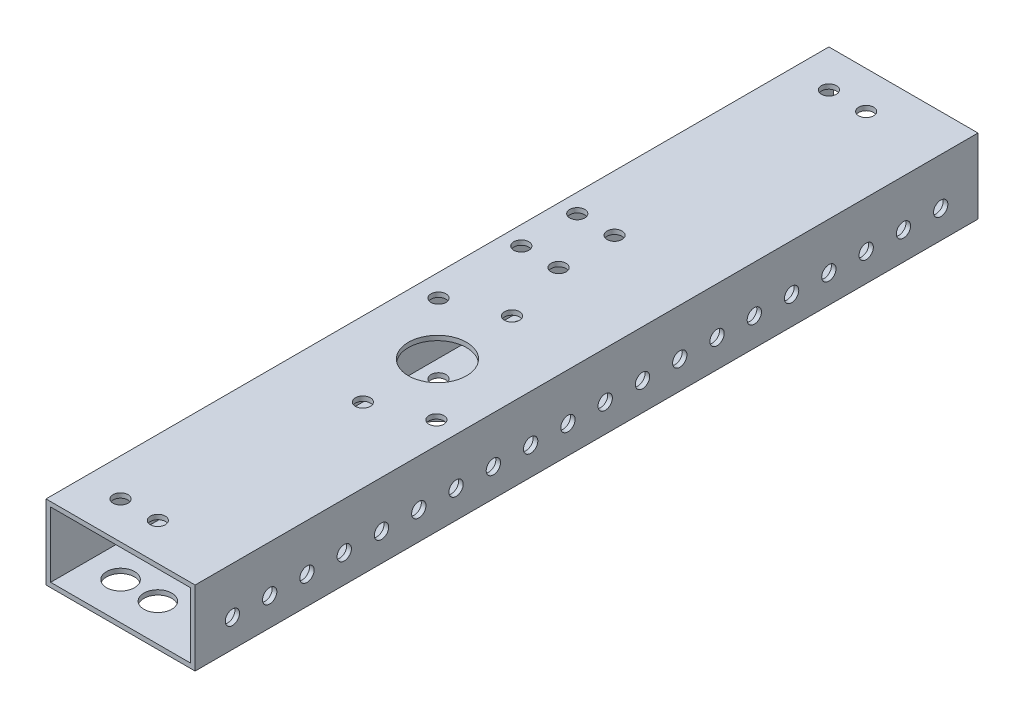
SolidWorks part; units mm, degrees
other "Markup1"
sketch "Sketch7" plane through (25.4, 12.7, -127) normal (0.9965, 0.0171, -0.0817) x (-0.082, 0.0128, -0.9966)
sketch "Sketch8" plane through (25.4, 12.7, -127) normal (0.9965, 0.0171, -0.0817) x (-0.082, 0.0128, -0.9966)
sketch "Sketch9" plane through (25.4, 12.7, -127) normal (0.9965, 0.0171, -0.0817) x (-0.082, 0.0128, -0.9966)
sketch "Sketch12" plane through (25.4, 12.7, -127) normal (0.9965, 0.0171, -0.0817) x (-0.082, 0.0128, -0.9966)
sketch "Sketch13" plane through (25.4, 12.7, -127) normal (0.9965, 0.0171, -0.0817) x (-0.082, 0.0128, -0.9966)
sketch "Sketch14" plane through (25.4, 12.7, -127) normal (0.9965, 0.0171, -0.0817) x (-0.082, 0.0128, -0.9966)
sketch "Sketch15" plane through (25.4, 12.7, -133.35) normal (0.9965, 0.0171, -0.0817) x (-0.082, 0.0128, -0.9966)
sketch "Sketch16" plane through (25.4, 12.7, -133.35) normal (0.9965, 0.0171, -0.0817) x (-0.082, 0.0128, -0.9966)
sketch "Sketch17" plane through (25.4, 12.7, -133.35) normal (0.9965, 0.0171, -0.0817) x (-0.082, 0.0128, -0.9966)
sketch "Sketch18" plane through (25.4, 12.7, -133.35) normal (0.9965, 0.0171, -0.0817) x (-0.082, 0.0128, -0.9966)
sketch "Sketch19" plane through (25.4, 12.7, -133.35) normal (0.9965, 0.0171, -0.0817) x (-0.082, 0.0128, -0.9966)
material "6061-T6 (SS)"
ref_plane "Front Plane" through (0, 0, 0) normal (0, 0, 1) x (1, 0, 0)
ref_plane "Top Plane" through (0, 0, 0) normal (0, 1, 0) x (1, 0, 0)
ref_plane "Right Plane" through (0, 0, 0) normal (1, 0, 0) x (0, 0, -1)
sketch "Sketch1" plane through (0, 0, 0) normal (0, 0, 1) x (1, 0, 0)
  line L0 (-23.8125, 11.1125) -> (23.8125, 11.1125)
  line L1 (-25.4, -12.7) -> (25.4, -12.7)
  line L2 (-25.4, -12.7) -> (-25.4, 12.7)
  line L3 (-25.4, 12.7) -> (25.4, 12.7)
  line L4 (25.4, -12.7) -> (25.4, 12.7)
  line L5 (-25.4, -12.7) -> (25.4, 12.7) construction
  line L6 (-25.4, 12.7) -> (25.4, -12.7) construction
  line L7 (23.8125, -11.1125) -> (23.8125, 11.1125)
  line L8 (-23.8125, -11.1125) -> (23.8125, -11.1125)
  line L9 (-23.8125, -11.1125) -> (-23.8125, 11.1125)
  point P0 (0, 0)
  dimension "D1" = 50.8
  dimension "D2" = 25.4
  dimension "D3" = 1.5875
extrude "Boss-Extrude1" add sketch "Sketch1" along normal mid plane 266.7
sketch "Sketch3" plane through (0, 12.7, 0) normal (0, 1, 0) x (1, 0, 0)
  line L0 (25.4, 133.35) -> (-25.4, 133.35) construction
  line L1 (25.4, -133.35) -> (-25.4, -133.35) construction
  line L3 (-25.4, -133.35) -> (-25.4, 133.35) construction
  line L4 (25.4, -133.35) -> (25.4, 133.35) construction
  circle A0 centre (-12.7, -120.65) radius 2.5527
  circle A1 centre (0, -120.65) radius 2.5527
  circle A2 centre (-12.7, 120.65) radius 2.5527
  circle A3 centre (0, 120.65) radius 2.5527
  dimension "D5" = 5.1054
  dimension "D1" = 12.7
  dimension "D2" = 12.7
  dimension "D3" = 12.7
  dimension "D4" = 12.7
  dimension "D6" = 12.7
  dimension "D7" = 12.7
  dimension "D8" = 12.7
  dimension "D9" = 25.4
  dimension "D10" = 12.7
  dimension "D11" = 25.4
extrude "Cut-Extrude1" cut sketch "Sketch3" against normal up to surface (1.5875 mm away) up to face at (0, 11.1125, 0)
sketch "Sketch5" plane through (0, -12.7, 0) normal (0, -1, 0) x (1, 0, 0)
  circle A0 centre (-12.7, -120.65) radius 2.5527 construction
  circle A1 centre (0, -120.65) radius 2.5527 construction
  circle A2 centre (0, 120.65) radius 2.5527 construction
  circle A3 centre (-12.7, 120.65) radius 2.5527 construction
  circle A4 centre (-12.7, -120.65) radius 2.5527
  circle A5 centre (0, -120.65) radius 2.5527
  circle A6 centre (0, 120.65) radius 2.5527
  circle A7 centre (-12.7, 120.65) radius 2.5527
  circle A8 centre (-12.7, 120.65) radius 4.7625
  circle A9 centre (0, 120.65) radius 4.7625
  circle A10 centre (0, -120.65) radius 4.7625
  circle A11 centre (-12.7, -120.65) radius 4.7625
  dimension "D1" = 9.525
extrude "Cut-Extrude2" cut sketch "Sketch5" against normal up to surface (1.5875 mm away) contours A10 A5 | A5 | A11 A4 | A4 | A6 | A9 A6 | A8 A7 | A7 region at (-12.7, -12.7, -120.65) region at (0, -12.7, -120.65) region at (0, -12.7, 120.65) region at (-12.7, -12.7, 120.65) region at (-17.3278, -12.7, 120.65) region at (-4.6278, -12.7, 120.65) region at (-4.6278, -12.7, -120.65) region at (-17.3278, -12.7, -120.65) up to face at (0, -11.1125, 0)
sketch "Sketch6" plane through (25.4, 0, 0) normal (1, 0, 0) x (0, 0, -1)
  line L0 (-133.35, -12.7) -> (-133.35, 12.7) construction
  line L1 (-133.35, -12.7) -> (133.35, -12.7) construction
  line L2 (0, 12.7) -> (0, -12.7) construction
  line L3 (-133.35, 12.7) -> (133.35, 12.7) construction
  circle A0 centre (-120.65, -3.175) radius 2.4384
  circle A19 centre (-107.95, -3.175) radius 2.4384
  circle A20 centre (-95.25, -3.175) radius 2.4384
  circle A21 centre (-82.55, -3.175) radius 2.4384
  circle A22 centre (-69.85, -3.175) radius 2.4384
  circle A23 centre (-57.15, -3.175) radius 2.4384
  circle A24 centre (-44.45, -3.175) radius 2.4384
  circle A25 centre (-31.75, -3.175) radius 2.4384
  circle A26 centre (-19.05, -3.175) radius 2.4384
  circle A27 centre (-6.35, -3.175) radius 2.4384
  circle A28 centre (6.35, -3.175) radius 2.4384
  circle A29 centre (19.05, -3.175) radius 2.4384
  circle A30 centre (31.75, -3.175) radius 2.4384
  circle A31 centre (44.45, -3.175) radius 2.4384
  circle A32 centre (57.15, -3.175) radius 2.4384
  circle A33 centre (69.85, -3.175) radius 2.4384
  circle A34 centre (82.55, -3.175) radius 2.4384
  circle A35 centre (95.25, -3.175) radius 2.4384
  circle A36 centre (107.95, -3.175) radius 2.4384
  circle A37 centre (120.65, -3.175) radius 2.4384
  dimension "D1" = 4.8768
  dimension "D5" = 12.7
  dimension "D2" = 12.7
  dimension "D3" = 9.525
  dimension "D4" = 20
extrude "Cut-Extrude3" cut sketch "Sketch6" against normal up to next contours A0 | A19 | A20 | A21 | A23 | A22 | A24 | A25 | A26 | A27 | A28 | A29 | A30 | A31 | A32 | A37 | A36 | A35 | A34 | A33 | A24 | A33 region at (25.4, -3.175, 120.65) region at (25.4, -3.175, 107.95) region at (25.4, -3.175, 95.25) region at (25.4, -3.175, 82.55) region at (25.4, -3.175, 69.85) region at (25.4, -3.175, 57.15) region at (25.4, -3.175, 44.45) region at (25.4, -3.175, 31.75) region at (25.4, -3.175, 19.05) region at (25.4, -3.175, 6.35) region at (25.4, -3.175, -6.35) region at (25.4, -3.175, -19.05) region at (25.4, -3.175, -31.75) region at (25.4, -3.175, -44.45) region at (25.4, -3.175, -57.15) region at (25.4, -3.175, -69.85) region at (25.4, -3.175, -82.55) region at (25.4, -3.175, -95.25) region at (25.4, -3.175, -107.95) region at (25.4, -3.175, -120.65)
sketch "Sketch11" plane through (0, 12.7, 0) normal (0, 1, 0) x (1, 0, 0)
  line L0 (-25.4, -133.35) -> (-25.4, 133.35) construction
  line L1 (-6.35, 41.275) -> (-6.35, 22.225) construction
  line L2 (0, 0) -> (0, -50.8) construction
  line L3 (25.4, 133.35) -> (-25.4, 133.35) construction
  line L5 (-19.05, 41.275) -> (-3.7973, 41.275) construction
  line L6 (-19.05, 41.275) -> (-19.05, 22.225) construction
  line L7 (-19.05, 22.225) -> (-3.7973, 22.225) construction
  line L9 (-19.05, 41.275) -> (-16.8611, 39.9616) construction
  line L10 (-19.05, 22.225) -> (-16.8611, 23.5384) construction
  line L13 (-15.875, -34.925) -> (-15.875, -15.875) construction
  line L14 (17.78, -43.5392) -> (-17.78, -7.2608) construction
  circle A0 centre (0, -25.4) radius 9.906
  circle A1 centre (0, 0) radius 2.5527
  circle A2 centre (0, -50.8) radius 2.5527
  circle A4 centre (-19.05, 22.225) radius 2.5527
  circle A5 centre (-19.05, 41.275) radius 2.5527
  circle A7 centre (-6.35, 22.225) radius 2.5527
  circle A8 centre (-6.35, 41.275) radius 2.5527
  circle A13 centre (-17.78, -7.2608) radius 2.5527
  circle A14 centre (17.78, -43.5392) radius 2.5527
  point P2 (0, -25.4)
  point P8 (-3.175, 31.75)
  point P24 (0, -25.4)
  dimension "D1" = 19.812
  dimension "D3" = 5.1054
  dimension "D4" = 25.4
  dimension "D5" = 19.05
  dimension "D6" = 5.1054
  dimension "D7" = 12.7
  dimension "D10" = 7.62
  dimension "D2" = 25.4
  dimension "D8" = 101.6
  dimension "D9" = 6.35
  dimension "D11" = 15.875
  dimension "D12" = 22.225
  dimension "1" = 25.4
extrude "Cut-Extrude4" cut sketch "Sketch11" against normal through all
